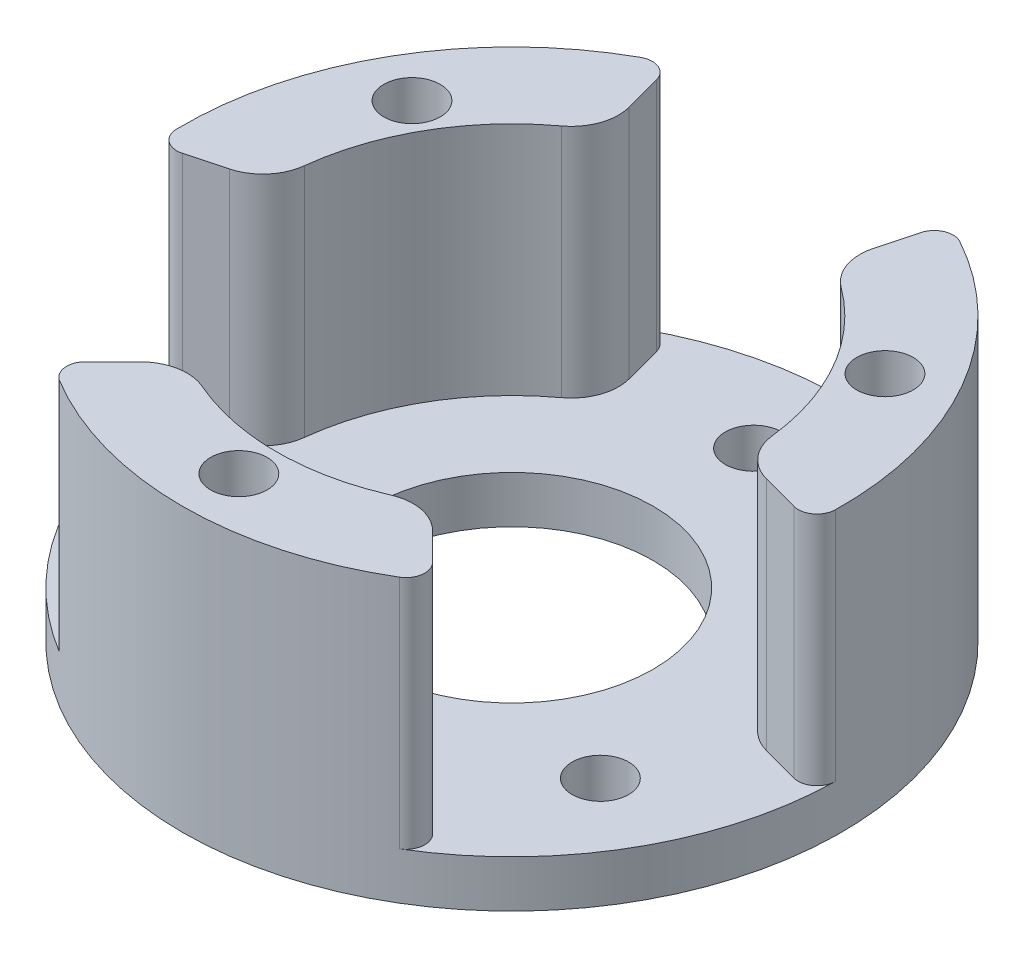
SolidWorks part; units mm, degrees
ref_plane "Front Plane" through (0, 0, 0) normal (0, 0, 1) x (1, 0, 0)
ref_plane "Top Plane" through (0, 0, 0) normal (0, 1, 0) x (1, 0, 0)
ref_plane "Right Plane" through (0, 0, 0) normal (1, 0, 0) x (0, 0, -1)
sketch "Sketch1" plane through (0, 0, 0) normal (0, 1, 0) x (1, 0, 0)
  line L0 (0, 25.66) -> (0, 0) construction
  line L1 (22.2222, -12.83) -> (0, 0) construction
  line L2 (-22.2222, -12.83) -> (0, 0) construction
  circle A0 centre (0, 0) radius 25.66 construction
  circle A1 centre (0, 0) radius 35
  circle A2 centre (0, 25.66) radius 3
  circle A3 centre (22.2222, -12.83) radius 3
  circle A4 centre (-22.2222, -12.83) radius 3
  circle A5 centre (0, 0) radius 15
  point P3 (0, 25.66)
  point P7 (22.2222, -12.83)
  point P9 (-22.2222, -12.83)
  point P11 (0, 0)
  point P18 (0, 0)
  dimension "D3" = 70
  dimension "D4" = 6
  dimension "D6" = 30
  dimension "D2" = 25.66
  dimension "D1" = 3
  dimension "D5" = 3
extrude "Boss-Extrude1" add sketch "Sketch1" along normal blind 5
sketch "Sketch2" plane through (0, 5, 0) normal (0, -1, 0) x (1, 0, 0)
  line L0 (0, 0) -> (0, 35) construction
  line L1 (15.5355, 23.9599) -> (20.1755, 28.5998)
  line L2 (-15.5355, 23.9599) -> (-20.1755, 28.5998)
  line L3 (28.5177, 1.4742) -> (34.8559, 3.1725)
  line L4 (12.9821, -25.4341) -> (14.6805, -31.7724)
  line L5 (-12.9821, -25.4341) -> (-14.6805, -31.7724)
  line L6 (-28.5177, 1.4742) -> (-34.8559, 3.1725)
  circle A0 centre (0, 0) radius 35 construction
  arc A1 (-20.1755, 28.5998) -> (20.1755, 28.5998) centre (0, 0) cw
  arc A2 (-10, 22.9129) -> (10, 22.9129) centre (0, 0) cw
  arc A3 (10, 22.9129) -> (15.5355, 23.9599) centre (12, 27.4955) ccw
  arc A4 (-10, 22.9129) -> (-15.5355, 23.9599) centre (-12, 27.4955) cw
  arc A5 (24.8431, -2.7962) -> (28.5177, 1.4742) centre (29.8118, -3.3554) cw
  arc A6 (34.8559, 3.1725) -> (14.6805, -31.7724) centre (0, 0) cw
  arc A7 (14.8431, -20.1167) -> (12.9821, -25.4341) centre (17.8118, -24.14) ccw
  arc A8 (24.8431, -2.7962) -> (14.8431, -20.1167) centre (0, 0) cw
  arc A9 (-14.8431, -20.1167) -> (-12.9821, -25.4341) centre (-17.8118, -24.14) cw
  arc A10 (-14.6805, -31.7724) -> (-34.8559, 3.1725) centre (0, 0) cw
  arc A11 (-24.8431, -2.7962) -> (-28.5177, 1.4742) centre (-29.8118, -3.3554) ccw
  arc A12 (-14.8431, -20.1167) -> (-24.8431, -2.7962) centre (0, 0) cw
  point P33 (0, 0)
  dimension "D1" = 5
  dimension "D2" = 25
  dimension "D3" = 45
  dimension "D4" = 20
  dimension "D5" = 3
extrude "Pegs" add sketch "Sketch2" against normal blind 24.9915
fillet "Fillet1" radius 2 6 edges at (-34.8559, 17.4958, 3.1725) (-14.6805, 17.4958, -31.7724) (14.6805, 17.4958, -31.7724) (34.8559, 17.4958, 3.1725) (20.1755, 17.4958, 28.5998) (-20.1755, 17.4958, 28.5998)
sketch "Sketch3" plane through (0, 0, 0) normal (0, -1, 0) x (1, 0, 0)
  line L0 (0, 0) -> (0, 29) construction
  line L1 (0, 0) -> (25.1147, -14.5) construction
  line L2 (0, 0) -> (-25.1147, -14.5) construction
  circle A0 centre (0, 0) radius 29 construction
  point P4 (0, 29)
  point P5 (25.1147, -14.5)
  point P7 (-25.1147, -14.5)
  point P8 (0, 0)
  dimension "D1" = 58
  dimension "D2" = 3
hole_wizard "Ø6.0mm Dowel Hole2" positions "Sketch3" profile "Sketch4" hole size "Ø6.0" standard "ANSI Metric" end condition through all
sketch "Sketch4" plane through (-25.1147, 0, -14.5) normal (1, 0, 0) x (0, 0, -1)
  line L0 (0, 0) -> (0, 29.9915)
  line L1 (0, 29.9915) -> (3, 29.9915)
  line L2 (3, 29.9915) -> (3, 0)
  line L5 (3, 0) -> (0, 0)
  line L11 (0, -6.35) -> (0, 107.95) construction
  dimension "Thru Hole Dia." = 6
  dimension "Thru Hole Depth" = 29.9915
sketch "Sketch5" plane through (0, 0, 0) normal (0, -1, 0) x (1, 0, 0)
  circle A0 centre (-25.1147, -14.5) radius 5
  circle A1 centre (0, 29) radius 5
  circle A2 centre (25.1147, -14.5) radius 5
  circle A3 centre (0, 0) radius 15 construction
  point P10 (0, 0)
  dimension "D1" = 10
  dimension "D2" = 3
extrude "Cut-Extrude1" cut sketch "Sketch5" against normal blind 2
